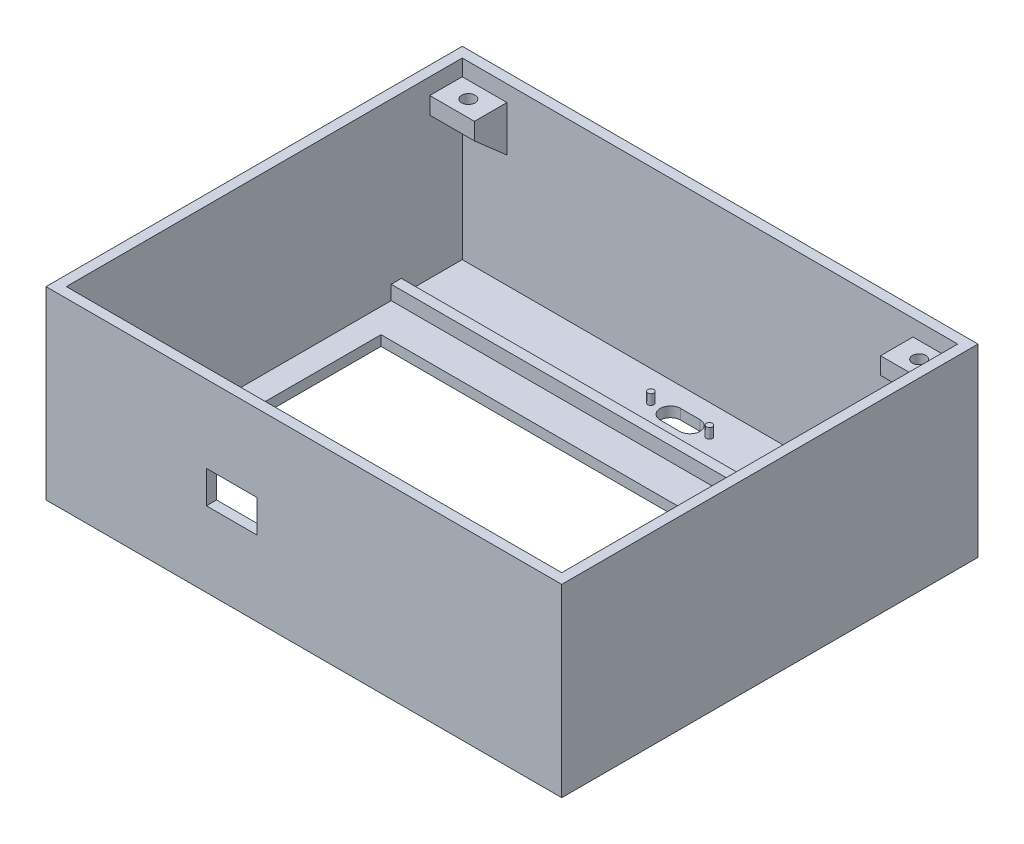
SolidWorks part; units mm, degrees
ref_plane "Front Plane" through (0, 0, 0) normal (0, 0, 1) x (1, 0, 0)
ref_plane "Top Plane" through (0, 0, 0) normal (0, 1, 0) x (1, 0, 0)
ref_plane "Right Plane" through (0, 0, 0) normal (1, 0, 0) x (0, 0, -1)
sketch "Sketch1" plane through (0, 0, 0) normal (0, 1, 0) x (1, 0, 0)
  line L1 (0, 0) -> (127, 0)
  line L2 (0, 0) -> (0, 85)
  line L3 (0, 85) -> (127, 85)
  line L4 (127, 0) -> (127, 85)
extrude "Boss-Extrude1" add sketch "Sketch1" along normal blind 2.5
sketch "Sketch2" plane through (0, 2.5, 0) normal (0, 1, 0) x (1, 0, 0)
  line L0 (0, 85) -> (127, 85)
  line L1 (127, 85) -> (127, 0)
  line L2 (127, 0) -> (0, 0)
  line L3 (0, 0) -> (0, 85)
  line L5 (2.5, 82.5) -> (124.5, 82.5)
  line L6 (2.5, 82.5) -> (2.5, 2.5)
  line L7 (2.5, 2.5) -> (124.5, 2.5)
  line L8 (124.5, 82.5) -> (124.5, 2.5)
  dimension "D1" = 2.5
  dimension "D2" = 2.5
  dimension "D3" = 2.5
  dimension "D4" = 2.5
extrude "Boss-Extrude2" add sketch "Sketch2" along normal blind 38.5
sketch "Sketch3" plane through (0, 0, 0) normal (0, -1, 0) x (-1, 0, 0)
  line L0 (-127, 85) -> (0, 85) construction
  line L1 (-8.5, 5.5) -> (-118.5, 5.5)
  line L2 (-8.5, 5.5) -> (-8.5, 74)
  line L3 (-8.5, 74) -> (-118.5, 74)
  line L4 (-118.5, 5.5) -> (-118.5, 74)
  line L6 (0, 0) -> (-127, 0) construction
  line L7 (-127, 0) -> (-127, 85) construction
  line L8 (0, 85) -> (0, 0) construction
  dimension "D1" = 11
  dimension "D2" = 5.5
  dimension "D3" = 8.5
  dimension "D4" = 8.5
extrude "Cut-Extrude1" cut sketch "Sketch3" against normal blind 2.5
sketch "Sketch6" plane through (0, 0, 0) normal (0, -1, 0) x (-1, 0, 0)
  line L8 (-61.1, 92.6537) -> (-65.9, 92.6537) construction
  line L9 (-61.1, 90.1537) -> (-65.9, 90.1537)
  line L10 (-61.1, 95.1537) -> (-65.9, 95.1537)
  arc A0 (-61.1, 90.1537) -> (-61.1, 95.1537) centre (-61.1, 92.6537) ccw
  arc A2 (-65.9, 95.1537) -> (-65.9, 90.1537) centre (-65.9, 92.6537) ccw
  point P1 (-63.5, 92.6537)
sketch "Sketch9" plane through (0, 0, -85) normal (0, 0, -1) x (-1, 0, 0)
  line L0 (-127, 0) -> (0, 0) construction
  line L1 (-127, 0) -> (0, 0)
  line L2 (-127, 0) -> (-127, 2.5)
  line L4 (0, 0) -> (0, 2.5)
  line L5 (-127, 41) -> (-127, 0) construction
  line L6 (0, 41) -> (0, 0) construction
  line L7 (-2.5, 2.5) -> (-124.5, 2.5)
  line L8 (-127, 41) -> (-124.5, 41)
  line L9 (-127, 41) -> (-127, 2.5)
  line L11 (-124.5, 41) -> (-124.5, 2.5)
  line L12 (0, 41) -> (-2.5, 41)
  line L13 (0, 41) -> (0, 2.5)
  line L15 (-2.5, 41) -> (-2.5, 2.5)
  dimension "D2" = 2.5
  dimension "D3" = 2.5
extrude "Boss-Extrude3" add sketch "Sketch9" along normal blind 15
sketch "Sketch10" plane through (0, 41, 0) normal (0, 1, 0) x (1, 0, 0)
  line L1 (2.5, 85) -> (124.5, 85)
  line L2 (2.5, 85) -> (2.5, 82.5)
  line L3 (2.5, 82.5) -> (124.5, 82.5)
  line L4 (124.5, 85) -> (124.5, 82.5)
extrude "Cut-Extrude2" cut sketch "Sketch10" against normal blind 35
sketch "Sketch11" plane through (0, 0, -100) normal (0, 0, -1) x (-1, 0, 0)
  line L1 (0, 0) -> (-127, 0)
  line L2 (0, 0) -> (0, 41)
  line L3 (0, 41) -> (-127, 41)
  line L4 (-127, 0) -> (-127, 41)
extrude "Boss-Extrude4" add sketch "Sketch11" along normal blind 2.5
sketch "Sketch13" plane through (0, 2.5, 0) normal (0, 1, 0) x (1, 0, 0)
  circle A0 centre (56.3, 92.6537) radius 0.75
  circle A1 centre (70.7, 92.6537) radius 0.75
  arc A2 (61.1, 95.1537) -> (61.1, 90.1537) centre (61.1, 92.6537) ccw construction
  dimension "D1" = 14.4
  dimension "D2" = 4.8
  dimension "D3" = 4.8
  dimension "D4" = 1.5
  dimension "D5" = 1.5
extrude "Cut-Extrude4" cut sketch "Sketch6" against normal blind 2.5
sketch "Sketch14" plane through (0, 2.5, 0) normal (0, 1, 0) x (1, 0, 0)
  line L1 (56, 87.1537) -> (71, 87.1537)
  line L2 (56, 87.1537) -> (56, 86.1537)
  line L3 (56, 86.1537) -> (71, 86.1537)
  line L4 (71, 87.1537) -> (71, 86.1537)
  arc A0 (61.1, 95.1537) -> (61.1, 90.1537) centre (61.1, 92.6537) ccw construction
  arc A1 (65.9, 90.1537) -> (65.9, 95.1537) centre (65.9, 92.6537) ccw construction
  dimension "D1" = 5.1
  dimension "D2" = 5.1
extrude "Cut-Extrude5" cut sketch "Sketch14" against normal blind 1.5
extrude "Boss-Extrude6" add sketch "Sketch13" along normal blind 2.5
sketch "Sketch17" plane through (0, 0, 0) normal (0, 0, 1) x (1, 0, 0)
  line L0 (0, 41) -> (0, 0) construction
  line L1 (39.5, 26.5) -> (52, 26.5)
  line L2 (39.5, 26.5) -> (39.5, 18.5)
  line L3 (39.5, 18.5) -> (52, 18.5)
  line L4 (52, 26.5) -> (52, 18.5)
  line L5 (0, 0) -> (127, 0) construction
  dimension "D1" = 39.5
  dimension "D2" = 18.5
  dimension "D3" = 8
  dimension "D4" = 12.5
extrude "Cut-Extrude6" cut sketch "Sketch17" against normal blind 2.5
sketch "Sketch19" plane through (0, 41, 0) normal (0, 1, 0) x (1, 0, 0)
  line L0 (0, 102.5) -> (127, 102.5)
  line L1 (127, 102.5) -> (127, 0)
  line L2 (127, 0) -> (0, 0)
  line L3 (0, 0) -> (0, 102.5)
  line L5 (2.5, 100) -> (124.5, 100)
  line L6 (2.5, 100) -> (2.5, 2.5)
  line L7 (2.5, 2.5) -> (124.5, 2.5)
  line L8 (124.5, 100) -> (124.5, 2.5)
extrude "Boss-Extrude7" add sketch "Sketch19" along normal blind 4.5
sketch "Sketch20" plane through (0, 0, -100) normal (0, 0, 1) x (1, 0, 0)
  line L0 (2.5, 45.5) -> (2.5, 2.5) construction
  line L1 (2.5, 41.5) -> (13.5, 41.5)
  line L2 (2.5, 41.5) -> (2.5, 37.3158)
  line L3 (2.5, 37.3158) -> (13.5, 37.3158)
  line L4 (13.5, 41.5) -> (13.5, 37.3158)
  line L5 (124.5, 45.5) -> (2.5, 45.5) construction
  line L6 (113.5, 37.3158) -> (124.5, 37.3158)
  line L7 (113.5, 41.5) -> (113.5, 37.3158)
  line L8 (113.5, 41.5) -> (124.5, 41.5)
  line L9 (124.5, 41.5) -> (124.5, 37.3158)
  dimension "D1" = 4
  dimension "D2" = 11
extrude "Boss-Extrude8" add sketch "Sketch20" along normal blind 8
sketch "Sketch22" plane through (0, 41.5, 0) normal (0, 1, 0) x (1, 0, 0)
  line L0 (124.5, 2.5) -> (124.5, 100) construction
  line L2 (2.5, 92) -> (2.5, 100) construction
  line L5 (13.5, 100) -> (2.5, 100) construction
  circle A0 centre (8, 96) radius 1.65
  circle A1 centre (119, 96) radius 1.65
  dimension "D1" = 4
  dimension "D2" = 5.5
  dimension "D4" = 5.5
  dimension "D5" = 3.3
  dimension "D3" = 2
extrude "Cut-Extrude7" cut sketch "Sketch22" against normal blind 5
sketch "Sketch23" plane through (2.5, 0, 0) normal (1, 0, 0) x (0, 0, -1)
  line L0 (92, 37.3158) -> (100, 37.3158)
  line L1 (100, 37.3158) -> (100, 2.5) construction
  line L2 (100, 37.3158) -> (100, 30.3158)
  line L3 (100, 30.3158) -> (92, 37.3158)
  dimension "D1" = 7
extrude "Boss-Extrude9" add sketch "Sketch23" along normal blind 11
sketch "Sketch24" plane through (124.5, 0, 0) normal (-1, 0, 0) x (0, 0, 1)
  line L3 (-92, 37.3158) -> (-100, 37.3158)
  line L4 (-92, 37.3158) -> (-100, 37.3158) construction
  line L5 (-100, 37.3158) -> (-100, 30.3158)
  line L6 (-100, 2.5) -> (-100, 37.3158) construction
  line L7 (-100, 30.3158) -> (-92, 37.3158)
  dimension "D1" = 7
extrude "Boss-Extrude10" add sketch "Sketch24" along normal blind 11
